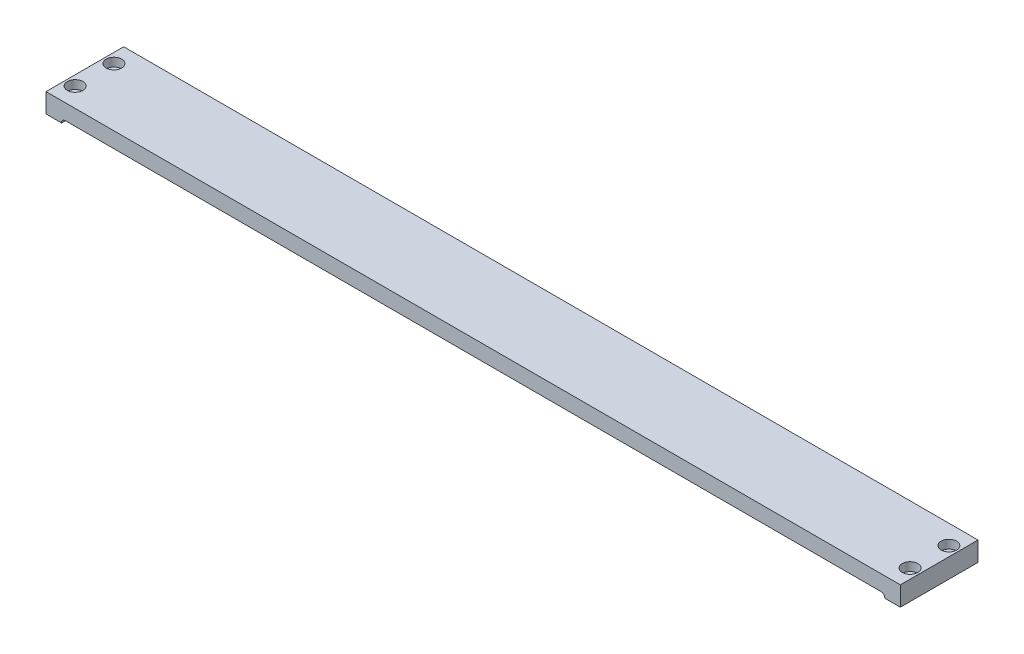
SolidWorks part; units mm, degrees
ref_plane "Front Plane" through (0, 0, 0) normal (0, 0, 1) x (1, 0, 0)
ref_plane "Top Plane" through (0, 0, 0) normal (0, 1, 0) x (1, 0, 0)
ref_plane "Right Plane" through (0, 0, 0) normal (1, 0, 0) x (0, 0, -1)
sketch "Sketch1" plane through (0, 0, 0) normal (0, 1, 0) x (1, 0, 0)
  line L1 (-220, -20) -> (220, -20)
  line L2 (-220, -20) -> (-220, 20)
  line L3 (-220, 20) -> (220, 20)
  line L4 (220, -20) -> (220, 20)
  line L5 (-220, -20) -> (220, 20) construction
  line L6 (-220, 20) -> (220, -20) construction
  point P0 (0, 0)
  dimension "D1" = 440
  dimension "D2" = 40
extrude "Boss-Extrude1" add sketch "Sketch1" along normal blind 10
sketch "Sketch2" plane through (0, 0, 20) normal (0, 0, 1) x (1, 0, 0)
  line L0 (-220, 0) -> (220, 0) construction
  line L1 (-212, 0) -> (212, 0)
  line L2 (-212, 0) -> (-212, 2)
  line L3 (-212, 2) -> (212, 2)
  line L4 (212, 0) -> (212, 2)
  line L5 (-220, 10) -> (-220, 0) construction
  line L6 (220, 10) -> (220, 0) construction
  dimension "D1" = 2
  dimension "D2" = 8
  dimension "D3" = 8
extrude "Cut-Extrude1" cut sketch "Sketch2" against normal blind 2
fillet "Fillet1" radius 2 2 edges at (-212, 2, 19) (212, 2, 19)
hole_wizard "CBORE for M4 Hex Socket Head Cap Screw1" positions "Sketch3" profile "Sketch4" counterbore size "M4" standard "DIN"
sketch "Sketch3" plane through (0, 10, 0) normal (0, 1, 0) x (1, 0, 0)
  line L0 (-5.5, 0) -> (5.5, 0) construction
  line L1 (-220, 20) -> (-220, -20) construction
  point P0 (-215, 10)
  point P2 (-215, -10)
  dimension "D1" = 10
  dimension "D2" = 10
  dimension "D3" = 5
sketch "Sketch4" plane through (-215, 10, -10) normal (1, 0, 0) x (0, 0, 1)
  line L0 (0, 0) -> (0, 15.3519)
  line L1 (0, 15.3519) -> (2.25, 14)
  line L2 (2.25, 14) -> (2.25, 4.4)
  line L3 (2.25, 4.4) -> (4, 4.4)
  line L4 (4, 4.4) -> (4, 0)
  line L5 (4, 0) -> (0, 0)
  line L10 (0, 15.3519) -> (-2.25, 14) construction
  line L11 (0, -6.35) -> (0, 107.95) construction
  dimension "Hole Dia." = 4.5
  dimension "Hole Depth" = 14
  dimension "C'Bore Dia." = 8
  dimension "C'Bore Depth" = 4.4
  dimension "Drill Angle" = 118
mirror "Mirror1" about plane through (0, 0, 0) normal (1, 0, 0) of "CBORE for M4 Hex Socket Head Cap Screw1"
hole_wizard "M4x0.7 Tapped Hole1" positions "Sketch5" profile "Sketch7" tap size "M4x0.7" standard "ANSI Metric"
sketch "Sketch5" plane through (0, 0, -20) normal (0, 0, -1) x (-1, 0, 0)
  line L0 (-220, 10) -> (220, 10) construction
  line L1 (0, 5.5) -> (0, -5.5) construction
  point P0 (125, 5)
  point P2 (0, 5)
  point P4 (-125, 5)
  dimension "D1" = 5
  dimension "D2" = 125
  dimension "D3" = 125
sketch "Sketch7" plane through (-125, 5, -20) normal (1, 0, 0) x (0, 1, 0)
  line L0 (0, 0) -> (0, 14.9914)
  line L1 (0, 14.9914) -> (1.65, 14)
  line L2 (1.65, 14) -> (1.65, 0)
  line L5 (1.65, 0) -> (0, 0)
  line L10 (0, 14.9914) -> (-1.65, 14) construction
  line L11 (0, -6.35) -> (0, 107.95) construction
  dimension "Tap Drill Dia." = 3.3
  dimension "Tap Drill Depth" = 14
  dimension "Drill Angle" = 118
cosmetic thread "Hole Thread1" parameters "D1"=12, "D2"=4
cosmetic thread "Hole Thread2" parameters "D1"=12, "D2"=4
cosmetic thread "Hole Thread3" parameters "D1"=12, "D2"=4
